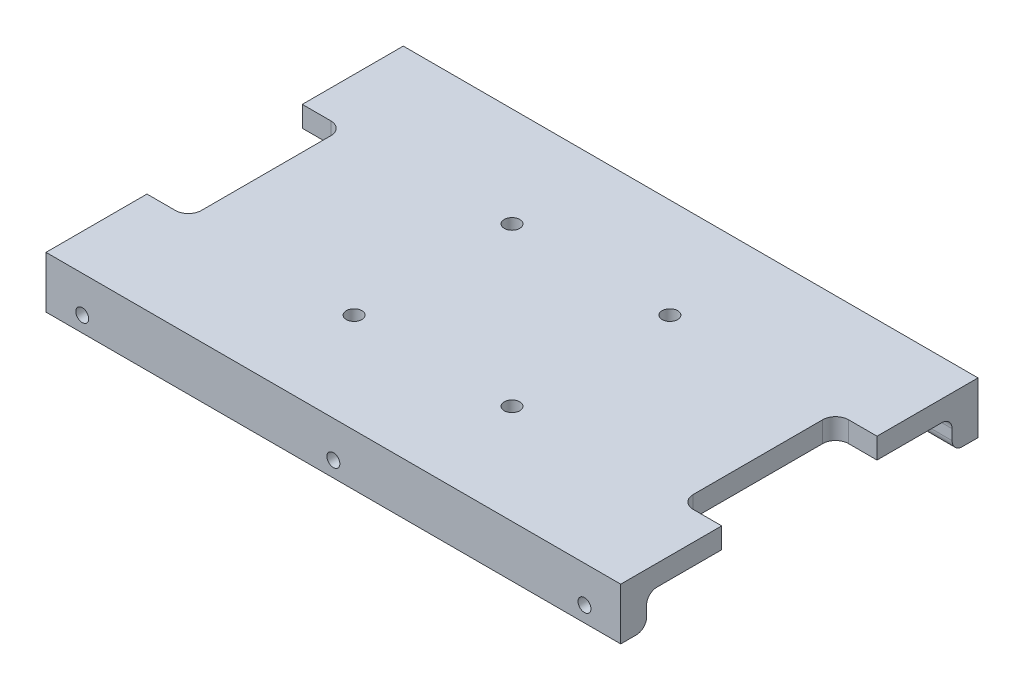
SolidWorks part; units mm, degrees
ref_plane "Front Plane" through (0, 0, 0) normal (0, 0, 1) x (1, 0, 0)
ref_plane "Top Plane" through (0, 0, 0) normal (0, 1, 0) x (1, 0, 0)
ref_plane "Right Plane" through (0, 0, 0) normal (1, 0, 0) x (0, 0, -1)
sketch "Sketch1" plane through (0, 0, 0) normal (1, 0, 0) x (0, 0, -1)
  line L1 (-69, 0) -> (-69, -10)
  line L2 (-69, -10) -> (-64, -10)
  line L3 (-64, -10) -> (-64, -4)
  line L4 (-64, -4) -> (-5, -4)
  line L5 (-5, -4) -> (-5, -10)
  line L6 (-5, -10) -> (0, -10)
  line L7 (0, -10) -> (0, 0)
  line L8 (0, 0) -> (-69, 0)
  dimension "D1" = 69
  dimension "D2" = 10
  dimension "D3" = 5
  dimension "D4" = 5
  dimension "D5" = 10
  dimension "D6" = 4
extrude "Boss-Extrude1" add sketch "Sketch1" along normal blind 111
sketch "Sketch2" plane through (0, 0, 0) normal (0, 0, 1) x (1, 0, 0)
  line L0 (0, 0) -> (0, -10) construction
  line L1 (111, -10) -> (0, -10) construction
  circle A0 centre (7, -7) radius 1.25
  circle A1 centre (55.5, -7) radius 1.25
  circle A2 centre (104, -7) radius 1.25
  dimension "D1" = 2.5
  dimension "D2" = 7
  dimension "D3" = 3
  dimension "D4" = 48.5
  dimension "D5" = 48.5
extrude "Cut-Extrude1" cut sketch "Sketch2" against normal through all and the other way through all
fillet "Fillet1" radius 2 4 edges at (55.5, -10, 5) (55.5, -10, 64) (55.5, -4, 5) (55.5, -4, 64)
sketch "Sketch3" plane through (0, -4, 0) normal (0, -1, 0) x (1, 0, 0)
  line L0 (0, 62) -> (0, 7) construction
  line L1 (0, 49.5) -> (5.5, 49.5)
  line L2 (0, 49.5) -> (0, 19.5)
  line L3 (0, 19.5) -> (5.5, 19.5)
  line L4 (8, 47) -> (8, 22)
  line L5 (111, 62) -> (111, 7) construction
  line L6 (111, 49.5) -> (105.5, 49.5)
  line L7 (111, 49.5) -> (111, 19.5)
  line L8 (111, 19.5) -> (105.5, 19.5)
  line L9 (103, 47) -> (103, 22)
  line L10 (6.25, 62) -> (0, 62) construction
  line L12 (111, 62) -> (104.75, 62) construction
  arc A0 (105.5, 19.5) -> (103, 22) centre (105.5, 22) cw
  arc A1 (105.5, 49.5) -> (103, 47) centre (105.5, 47) ccw
  arc A2 (5.5, 19.5) -> (8, 22) centre (5.5, 22) ccw
  arc A3 (5.5, 49.5) -> (8, 47) centre (5.5, 47) cw
  point P20 (103, 49.5)
  point P25 (8, 49.5)
  dimension "D7" = 2.5
  dimension "D1" = 8
  dimension "D2" = 8
  dimension "D3" = 30
  dimension "D4" = 30
  dimension "D5" = 12.5
  dimension "D6" = 12.5
extrude "Cut-Extrude2" cut sketch "Sketch3" against normal through all
sketch "Sketch4" plane through (0, -4, 0) normal (0, -1, 0) x (1, 0, 0)
  line L0 (8, 34.5) -> (103, 34.5) construction
  line L1 (8, 22) -> (8, 47) construction
  line L2 (103, 47) -> (103, 22) construction
  line L3 (55.5, 34.5) -> (55.5, 6.9843) construction
  line L4 (55.5, 34.5) -> (55.5, 62.0157) construction
  circle A0 centre (70.75, 49.75) radius 1.5
  circle A1 centre (70.75, 19.25) radius 1.5
  circle A2 centre (40.25, 19.25) radius 1.5
  circle A3 centre (40.25, 49.75) radius 1.5
  spline S0 degree 3 poles (54.75, 7) (55, 7) (55.25, 6.9843) (55.75, 6.9843) (55.9999, 7) (56.25, 7) knots 0 0 0 0 0.5 0.5 1 1 1 1 construction
  spline S1 degree 3 poles (56.25, 62) (55.9999, 62) (55.75, 62.0157) (55.25, 62.0157) (55, 62) (54.75, 62) knots 0 0 0 0 0.5 0.5 1 1 1 1 construction
  point P21 (0, 0)
  point P22 (0, 0)
  point P23 (0, 0)
  dimension "D1" = 3
  dimension "D2" = 30.5
  dimension "D3" = 30.5
  dimension "D4" = 15.25
  dimension "D5" = 15.25
extrude "Cut-Extrude3" cut sketch "Sketch4" against normal through all
